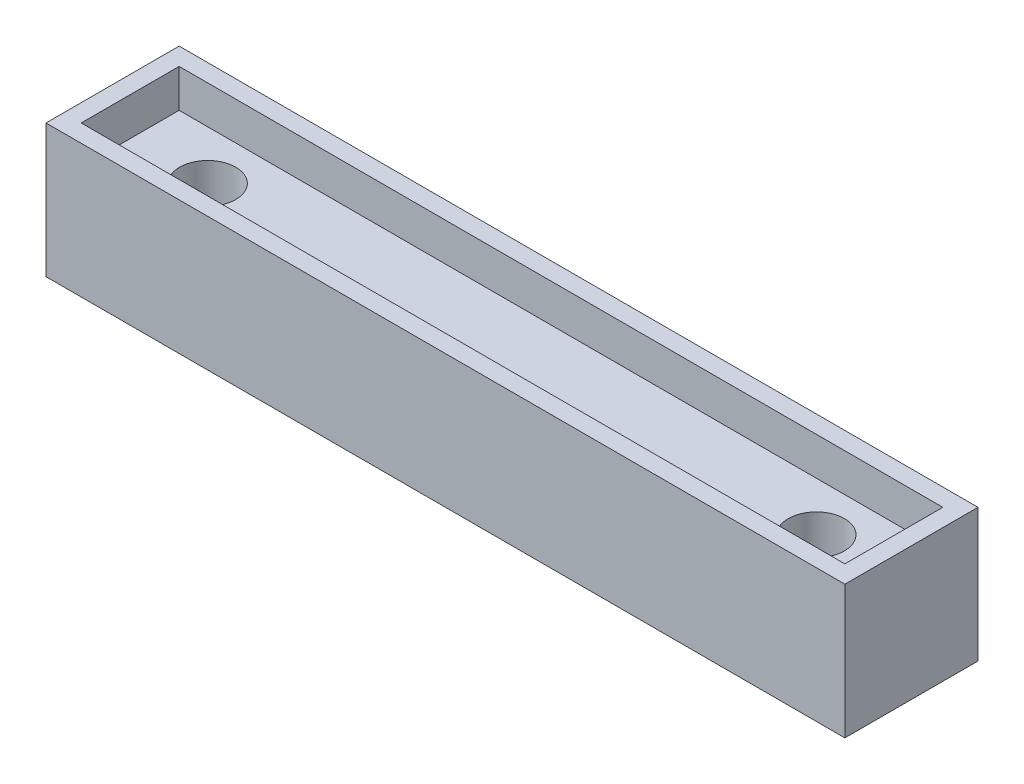
SolidWorks part; units mm, degrees
ref_plane "Front Plane" through (0, 0, 0) normal (0, 0, 1) x (1, 0, 0)
ref_plane "Top Plane" through (0, 0, 0) normal (0, 1, 0) x (1, 0, 0)
ref_plane "Right Plane" through (0, 0, 0) normal (1, 0, 0) x (0, 0, -1)
sketch "Sketch1" plane through (0, 0, 0) normal (0, 1, 0) x (1, 0, 0)
  line L0 (6.8056, 28.3123) -> (65.3062, -8.2429) construction
  line L1 (0, 7) -> (42, 7)
  line L2 (0, 7) -> (0, 0)
  line L3 (0, 0) -> (42, 0)
  line L4 (42, 7) -> (42, 0)
  line L5 (42, 0) -> (44.8404, 4.5455) construction
  dimension "D1" = 7
  dimension "D2" = 42
  dimension "D3" = 32
  dimension "D4" = 5.36
extrude "Riser" add sketch "Sketch1" along normal blind 7
sketch "Sketch2" plane through (0, 0, 0) normal (0, -1, 0) x (1, 0, 0)
  line L0 (0, -7) -> (0, 0) construction
  line L1 (21, 0) -> (21, -7) construction
  line L2 (0, 0) -> (42, 0) construction
  line L3 (42, -7) -> (0, -7) construction
  circle A0 centre (5, -3.5) radius 1.475
  circle A1 centre (37, -3.5) radius 1.475
  point P6 (0, -3.5)
  dimension "D2" = 2.95
  dimension "D1" = 5
extrude "Mounting Holes" cut sketch "Sketch2" against normal through all
sketch "Sketch3" plane through (0, 7, 0) normal (0, 1, 0) x (1, 0, 0)
  line L0 (41.075, 6.075) -> (0.925, 6.075)
  line L1 (0.925, 6.075) -> (0.925, 0.925)
  line L2 (0.925, 0.925) -> (41.075, 0.925)
  line L3 (41.075, 0.925) -> (41.075, 6.075)
  line L4 (0, 7) -> (0, 0)
  line L5 (0, 0) -> (42, 0)
  line L6 (42, 0) -> (42, 7)
  line L7 (42, 7) -> (0, 7)
  line L8 (0, 7) -> (0, 0)
  line L9 (0, 0) -> (42, 0)
  line L10 (42, 0) -> (42, 7)
  line L11 (42, 7) -> (0, 7)
  dimension "D1" = 0
  dimension "D2" = 0.925
extrude "Recess (4-Sides)" cut sketch "Sketch3" against normal blind 2 contours L0 L1 L2 L3
sketch "Sketch4" [suppressed] plane through (0, 7, 0) normal (0, 1, 0) x (1, 0, 0)
  line L0 (0, 0) -> (42, 0) construction
  line L1 (0.925, 6.075) -> (41.075, 6.075)
  line L2 (0.925, 6.075) -> (0.925, 0)
  line L3 (0.925, 0) -> (41.075, 0)
  line L4 (41.075, 6.075) -> (41.075, 0)
  line L5 (0, 7) -> (0, 0) construction
  line L6 (42, 0) -> (42, 7) construction
  line L7 (42, 7) -> (0, 7) construction
  dimension "D1" = 0.925
  dimension "D2" = 0.925
  dimension "D3" = 0.925
extrude "Recess (3-Sides)" [suppressed] cut sketch "Sketch4" against normal blind 2
sketch "Sketch5" [suppressed] plane through (0, 0, 0) normal (0, -1, 0) x (1, 0, 0)
  line L1 (10, -1.5) -> (32, -1.5)
  line L2 (10, -1.5) -> (10, -5.5)
  line L3 (10, -5.5) -> (32, -5.5)
  line L4 (32, -1.5) -> (32, -5.5)
  point P4 (37, -3.5)
  point P5 (5, -3.5)
  point P6 (10, -3.5)
  point P9 (32, -3.5)
  dimension "D1" = 5
  dimension "D2" = 5
  dimension "D3" = 4
extrude "Alignment Tab" [suppressed] add sketch "Sketch5" along normal blind 3.2
